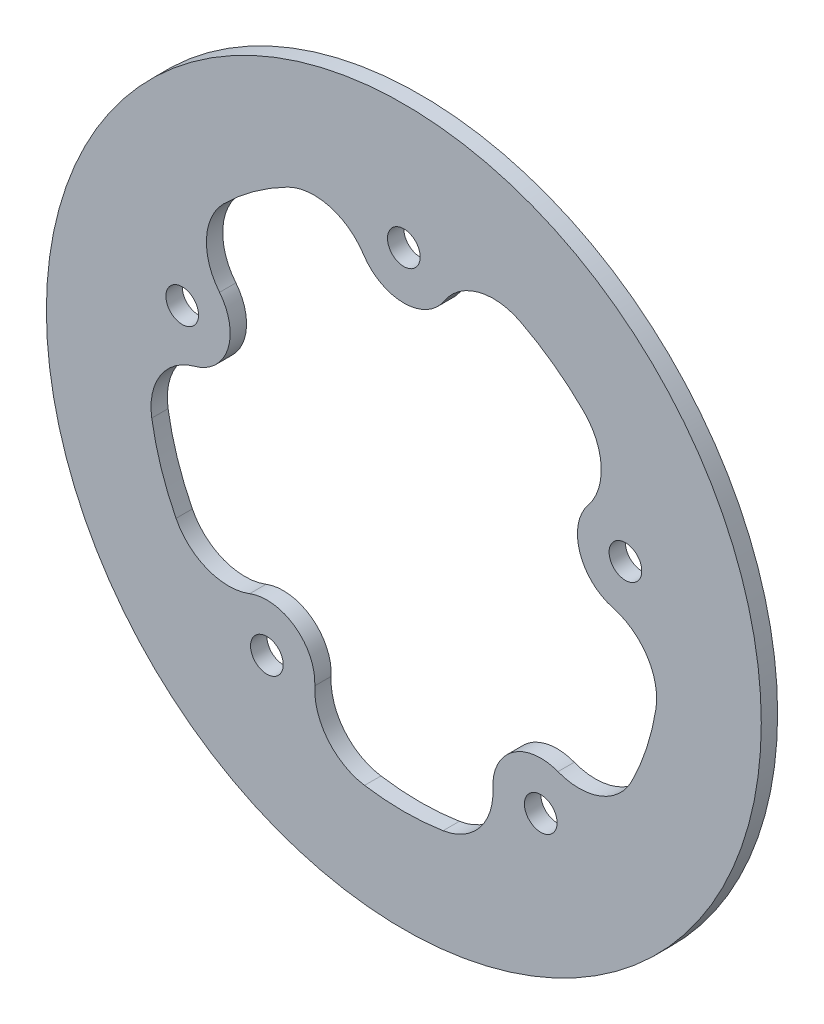
SolidWorks part; units mm, degrees
material "Alloy Steel (SS)"
ref_plane "Front Plane" through (0, 0, 0) normal (0, 0, 1) x (1, 0, 0)
ref_plane "Top Plane" through (0, 0, 0) normal (0, 1, 0) x (1, 0, 0)
ref_plane "Right Plane" through (0, 0, 0) normal (1, 0, 0) x (0, 0, -1)
sketch "Sketch1" plane through (0, 0, 0) normal (0, 0, 1) x (1, 0, 0)
  line L0 (0, 0) -> (0, 28.9725) construction
  line L1 (0, 0) -> (27.5545, 8.953) construction
  line L2 (0, 0) -> (17.0296, -23.4393) construction
  line L3 (0, 0) -> (-17.0296, -23.4393) construction
  line L4 (0, 0) -> (-27.5545, 8.953) construction
  circle A0 centre (0, 0) radius 44.45
  circle A1 centre (0, 0) radius 31.75
  circle A2 centre (0, 28.9725) radius 2.032
  arc A3 (5.0014, 25.723) -> (-5.0014, 25.723) centre (0, 28.9725) cw
  arc A4 (5.0014, 25.723) -> (14.49, 28.2507) centre (11.1459, 21.7308) cw
  arc A5 (-5.0014, 25.723) -> (-14.49, 28.2507) centre (-11.1459, 21.7308) ccw
  arc A6 (22.9185, 12.7054) -> (22.3904, 22.5107) centre (17.223, 17.3155) ccw
  arc A7 (26.0096, 3.1923) -> (22.9185, 12.7054) centre (27.5545, 8.953) cw
  circle A8 centre (27.5545, 8.953) radius 2.032
  arc A9 (26.0096, 3.1923) -> (31.3457, -5.0508) centre (24.1115, -3.8852) cw
  arc A10 (19.1658, -17.8706) -> (28.328, -14.3383) centre (21.7902, -11.0292) ccw
  arc A11 (11.0734, -23.7501) -> (19.1658, -17.8706) centre (17.0296, -23.4393) cw
  circle A12 centre (17.0296, -23.4393) radius 2.032
  arc A13 (11.0734, -23.7501) -> (4.8827, -31.3723) centre (3.7558, -24.132) cw
  arc A14 (-11.0734, -23.7501) -> (-4.8827, -31.3723) centre (-3.7558, -24.132) ccw
  arc A15 (-19.1658, -17.8706) -> (-11.0734, -23.7501) centre (-17.0296, -23.4393) cw
  circle A16 centre (-17.0296, -23.4393) radius 2.032
  arc A17 (-19.1658, -17.8706) -> (-28.328, -14.3383) centre (-21.7902, -11.0292) cw
  arc A18 (-26.0096, 3.1923) -> (-31.3457, -5.0508) centre (-24.1115, -3.8852) ccw
  arc A19 (-22.9185, 12.7054) -> (-26.0096, 3.1923) centre (-27.5545, 8.953) cw
  circle A20 centre (-27.5545, 8.953) radius 2.032
  arc A21 (-22.9185, 12.7054) -> (-22.3904, 22.5107) centre (-17.223, 17.3155) cw
  point P47 (0, 0)
  dimension "D1" = 88.9
  dimension "D2" = 63.5
  dimension "D3" = 4.064
  dimension "D5" = 5
extrude "Boss-Extrude1" add sketch "Sketch1" along normal blind 2.032 contours A0 A1 | A19 A21 A1 A18 A20 | A5 A3 A4 A1 A2 | A7 A9 A1 A6 A8 | A11 A13 A1 A10 A12 | A15 A17 A1 A14 A16 region at (-43.1928, 0, 0) region at (31.3559, -2.5101, 0) region at (9.1817, 29.1039, 0) region at (18.4918, -25.4518, 0) region at (-24.8332, 17.7254, 0) region at (-18.4918, -25.4518, 0)
